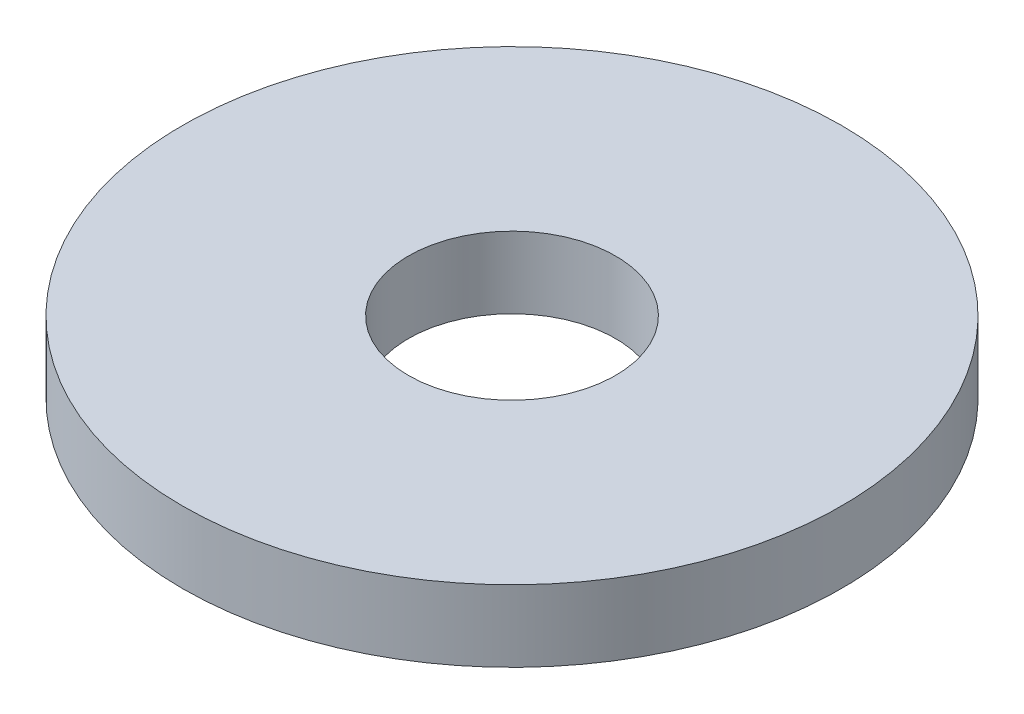
SolidWorks part; units mm, degrees
ref_plane "Front Plane" through (0, 0, 0) normal (0, 0, 1) x (1, 0, 0)
ref_plane "Top Plane" through (0, 0, 0) normal (0, 1, 0) x (1, 0, 0)
ref_plane "Right Plane" through (0, 0, 0) normal (1, 0, 0) x (0, 0, -1)
sketch "Sketch1" plane through (0, 0, 0) normal (0, 1, 0) x (1, 0, 0)
  circle A0 centre (0, 0) radius 87.5
  dimension "FLANGE_OD" = 175
extrude "Boss-Extrude1" add sketch "Sketch1" along normal blind 19
sketch "Sketch2" plane through (0, 0, 0) normal (0, 1, 0) x (1, 0, 0)
  circle A0 centre (0, 0) radius 27.5
  dimension "BORE_D" = 55
extrude "Cut-Extrude1" cut sketch "Sketch2" along normal through all
sketch "Sketch3" plane through (0, 19, 0) normal (0, 1, 0) x (1, 0, 0)
  circle A0 centre (0, 0) radius 21.169 construction
  circle A1 centre (-21.169, 0) radius 3.4813
  dimension "BOLT_D" = 6.9626
  dimension "BOLT_PCD" = 42.338
extrude "Cut-Extrude2" cut sketch "Sketch3" against normal blind 13.7213 rebuild error yes
pattern_circular "CirPattern1" count 5 over 360 rebuild error yes
